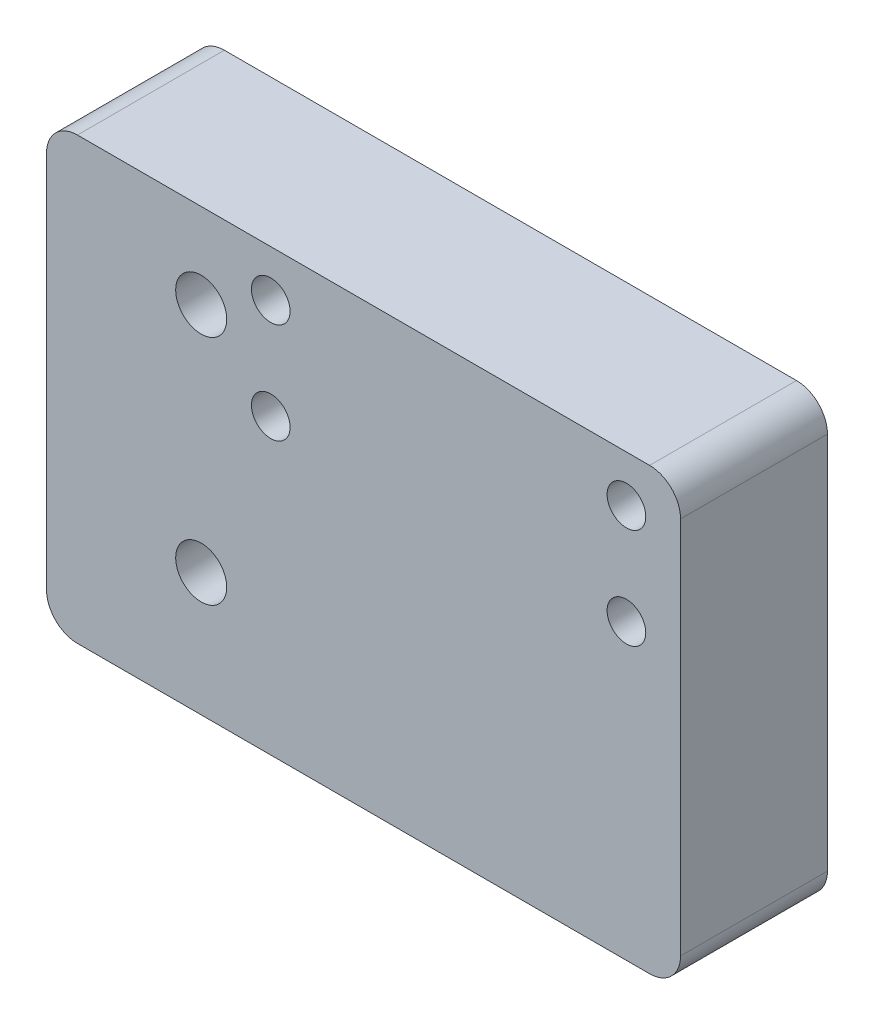
SolidWorks part; units mm, degrees
ref_plane "Front Plane" through (0, 0, 0) normal (0, 0, 1) x (1, 0, 0)
ref_plane "Top Plane" through (0, 0, 0) normal (0, 1, 0) x (1, 0, 0)
ref_plane "Right Plane" through (0, 0, 0) normal (1, 0, 0) x (0, 0, -1)
sketch "Sketch1" plane through (0, 0, 0) normal (0, 0, 1) x (1, 0, 0)
  line L1 (62, 68.7452) -> (-20, 68.7452)
  line L2 (62, 68.7452) -> (62, 8.7452)
  line L3 (62, 8.7452) -> (-20, 8.7452)
  line L4 (-20, 68.7452) -> (-20, 8.7452)
  dimension "D1" = 60
extrude "Boss-Extrude1" add sketch "Sketch1" along normal blind 19
hole_wizard "Tap Drill for M6 Tap1" positions "Sketch4" profile "Sketch3" hole size "M6" standard "ISO" end condition through all
sketch "Sketch4" plane through (0, 0, 19) normal (0, 0, 1) x (1, 0, 0)
  point P0 (9, 58.7452)
  point P3 (55, 58.7452)
  point P6 (55, 58.7452)
  point P9 (9, 58.7452)
  point P13 (55, 45.7452)
  point P15 (9, 45.7452)
sketch "Sketch3" plane through (9, 58.7452, 19) normal (1, 0, 0) x (0, -1, 0)
  line L0 (0, 0) -> (0, 19)
  line L1 (0, 19) -> (2.5, 19)
  line L2 (2.5, 19) -> (2.5, 0)
  line L5 (2.5, 0) -> (0, 0)
  line L11 (0, -6.35) -> (0, 107.95) construction
  dimension "Thru Hole Dia." = 5
  dimension "Thru Hole Depth" = 19
hole_wizard "CSK for M6 Countersunk Flat Head Screw1" positions "Sketch5" profile "Sketch6" countersink size "M6" standard "ISO" end condition through all
sketch "Sketch5" plane through (0, 0, 0) normal (0, 0, 1) x (1, 0, 0)
  line L0 (-20, 8.7452) -> (62, 8.7452) construction
  point P0 (0, 23.7452)
  point P2 (0, 53.7452)
  dimension "D1" = 30
  dimension "D2" = 15
sketch "Sketch6" plane through (0, 23.7452, 0) normal (1, 0, 0) x (0, 1, 0)
  line L0 (0, 0) -> (0, 19)
  line L1 (0, 19) -> (3.3, 19)
  line L2 (3.3, 19) -> (3.3, 3)
  line L3 (3.3, 3) -> (6.3, 0)
  line L5 (6.3, 0) -> (0, 0)
  line L6 (-3.3, 3) -> (-6.3, 0) construction
  line L11 (0, -6.35) -> (0, 107.95) construction
  dimension "Thru Hole Dia." = 6.6
  dimension "Thru Hole Depth" = 19
  dimension "Near C'Sink Dia." = 12.6
  dimension "Near C'Sink Angle" = 90
sketch "Sketch7" plane through (0, 0, 0) normal (0, 0, -1) x (-1, 0, 0)
  line L0 (20, 68.7452) -> (20, 8.7452) construction
  line L1 (20, 68.7452) -> (-62, 68.7452)
  line L2 (20, 68.7452) -> (20, 64.7452)
  line L3 (20, 64.7452) -> (-62, 64.7452)
  line L4 (-62, 68.7452) -> (-62, 64.7452)
  line L5 (-62, 8.7452) -> (-62, 68.7452) construction
extrude "Cut-Extrude1" cut sketch "Sketch7" against normal through all
sketch "Sketch10" plane through (0, 0, 0) normal (0, 0, -1) x (-1, 0, 0)
  line L1 (-62, 8.7452) -> (20, 8.7452)
  line L2 (-62, 8.7452) -> (-62, 7.7952)
  line L3 (-62, 7.7952) -> (20, 7.7952)
  line L4 (20, 8.7452) -> (20, 7.7952)
extrude "Boss-Extrude2" add sketch "Sketch10" against normal blind 19
fillet "Fillet1" radius 4 4 edges at (-20, 7.7952, 9.5) (62, 7.7952, 9.5) (-20, 64.7452, 9.5) (62, 64.7452, 9.5)
hole_wizard "Tap Drill for M5 Tap1" positions "Sketch8" profile "Sketch9" hole size "M5" standard "ISO"
sketch "Sketch8" plane through (0, 7.7952, 0) normal (0, -1, 0) x (-1, 0, 0)
  point P0 (-42, -9.5)
sketch "Sketch9" plane through (42, 7.7952, 9.5) normal (1, 0, 0) x (0, 0, -1)
  line L0 (0, 0) -> (0, 31.2618)
  line L1 (0, 31.2618) -> (2.1, 30)
  line L2 (2.1, 30) -> (2.1, 0)
  line L5 (2.1, 0) -> (0, 0)
  line L10 (0, 31.2618) -> (-2.1, 30) construction
  line L11 (0, -6.35) -> (0, 107.95) construction
  dimension "Hole Dia." = 4.2
  dimension "Hole Depth" = 30
  dimension "Drill Angle" = 118
